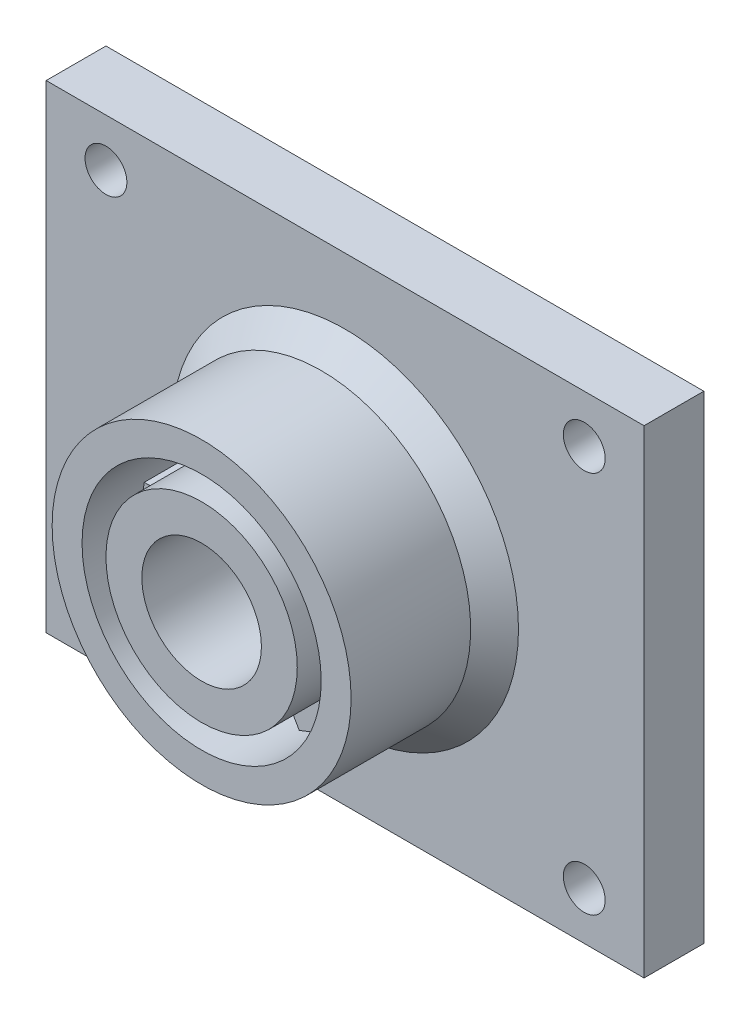
SolidWorks part; units mm, degrees
ref_plane "Alzado" through (0, 0, 0) normal (0, 0, 1) x (1, 0, 0)
ref_plane "Planta" through (0, 0, 0) normal (0, 1, 0) x (1, 0, 0)
ref_plane "Vista lateral" through (0, 0, 0) normal (1, 0, 0) x (0, 0, -1)
sketch "Croquis1" plane through (0, 0, 0) normal (0, 0, 1) x (1, 0, 0)
  line L0 (-20, 16) -> (20, 16) construction
  line L1 (-25, -20) -> (25, -20)
  line L2 (-25, -20) -> (-25, 20)
  line L3 (-25, 20) -> (25, 20)
  line L4 (25, -20) -> (25, 20)
  line L5 (-25, -20) -> (25, 20) construction
  line L6 (-25, 20) -> (25, -20) construction
  line L7 (-20, 16) -> (-20, -16) construction
  circle A0 centre (-20, 16) radius 1.75
  circle A1 centre (20, 16) radius 1.75
  circle A2 centre (20, -16) radius 1.75
  circle A3 centre (-20, -16) radius 1.75
  point P0 (0, 0)
  point P8 (0, 0)
  point P9 (0, 0)
  dimension "D3" = 3.5
  dimension "D5" = 2
  dimension "D1" = 50
  dimension "D2" = 40
  dimension "D4" = 4
  dimension "D6" = 2
extrude "Saliente-Extruir1" add sketch "Croquis1" along normal mid plane 5
sketch "Croquis2" plane through (0, 0, 2.5) normal (0, 0, 1) x (1, 0, 0)
  line L0 (-9.798, -2) -> (-7.746, -2)
  line L1 (-5, -8.6603) -> (5, 8.6603) construction
  line L8 (-5, 8.6603) -> (5, -8.6603) construction
  line L9 (-18.4242, 0) -> (18.4242, 0) construction
  line L10 (-9.798, 2) -> (-7.746, 2)
  line L11 (-3.1669, 9.4853) -> (-2.1409, 7.7082)
  line L12 (-6.631, 7.4853) -> (-5.605, 5.7082)
  line L13 (6.631, 7.4853) -> (5.605, 5.7082)
  line L14 (3.1669, 9.4853) -> (2.1409, 7.7082)
  line L15 (9.798, -2) -> (7.746, -2)
  line L16 (9.798, 2) -> (7.746, 2)
  line L17 (3.1669, -9.4853) -> (2.1409, -7.7082)
  line L18 (6.631, -7.4853) -> (5.605, -5.7082)
  line L19 (-6.631, -7.4853) -> (-5.605, -5.7082)
  line L20 (-3.1669, -9.4853) -> (-2.1409, -7.7082)
  line L21 (0, 0) -> (-7.746, 2) construction
  line L22 (0, 0) -> (-2.1409, 7.7082) construction
  circle A0 centre (0, 0) radius 10
  circle A1 centre (0, 0) radius 12.5
  circle A2 centre (0, 0) radius 8
  circle A3 centre (0, 0) radius 5
  dimension "D1" = 20
  dimension "D3" = 16
  dimension "D4" = 60
  dimension "D10" = 10
  dimension "D5" = 60
  dimension "D6" = 2
  dimension "D7" = 6
  dimension "D8" = 60
  dimension "D9" = 8
  dimension "D2" = 2.5
extrude "Saliente-Extruir2" add sketch "Croquis2" along normal blind 7 contours A2 L11 A0 L12 | A2 L13 A0 L14 | A2 L15 A0 L16 | A2 L17 A0 L18 | A2 L19 A0 L20 | A2 L10 A0 L0 | A1 A0 | A2 A3 region at (-8.9239, 0, 2.5) region at (-7.7737, 0, 2.5) region at (-4.4619, -7.7283, 2.5) region at (-4.4619, 7.7283, 2.5) region at (4.4619, -7.7283, 2.5) region at (4.4619, 7.7283, 2.5) region at (8.9239, 0, 2.5) region at (-12.1464, 0, 2.5)
sketch "Croquis4" plane through (0, 0, 9.5) normal (0, 0, 1) x (1, 0, 0)
  circle A0 centre (0, 0) radius 12.5 construction
  circle A1 centre (0, 0) radius 5
  circle A2 centre (0, 0) radius 5
  circle A3 centre (0, 0) radius 12.5
  circle A4 centre (0, 0) radius 10
  circle A7 centre (0, 0) radius 8
  circle A8 centre (0, 0) radius 8
  arc M4 (-7.746, -2) -> (-5.605, -5.7082) centre (0, 0) ccw
  arc M6 (-6.631, -7.4853) -> (-9.798, -2) centre (0, 0) cw
  arc M8 (-2.1409, -7.7082) -> (2.1409, -7.7082) centre (0, 0) ccw
  arc M10 (3.1669, -9.4853) -> (-3.1669, -9.4853) centre (0, 0) cw
  arc M12 (5.605, -5.7082) -> (7.746, -2) centre (0, 0) ccw
  arc M14 (9.798, -2) -> (6.631, -7.4853) centre (0, 0) cw
  arc M16 (7.746, 2) -> (5.605, 5.7082) centre (0, 0) ccw
  arc M18 (6.631, 7.4853) -> (9.798, 2) centre (0, 0) cw
  arc M20 (2.1409, 7.7082) -> (-2.1409, 7.7082) centre (0, 0) ccw
  arc M22 (-3.1669, 9.4853) -> (3.1669, 9.4853) centre (0, 0) cw
  arc M24 (-5.605, 5.7082) -> (-7.746, 2) centre (0, 0) ccw
  arc M26 (-9.798, 2) -> (-6.631, 7.4853) centre (0, 0) cw
  circle M27 centre (0, 0) radius 12.5
  circle M28 centre (0, 0) radius 5
  dimension "D1" = 0
  dimension "D2" = 2.5
  dimension "D3" = 3
extrude "Saliente-Extruir3" add sketch "Croquis4" along normal blind 5 contours A4 M27 M18 M14 M10 M6 M26 M22 | A8 M16 M20 M24 M4 M8 M12 M28 region at (-12.1464, 0, 9.5) region at (7.7118, -0.9795, 9.5)
chamfer "Chaflán1" distance 2 angle 45 1 edges at (-12.5, 0, 2.5)
